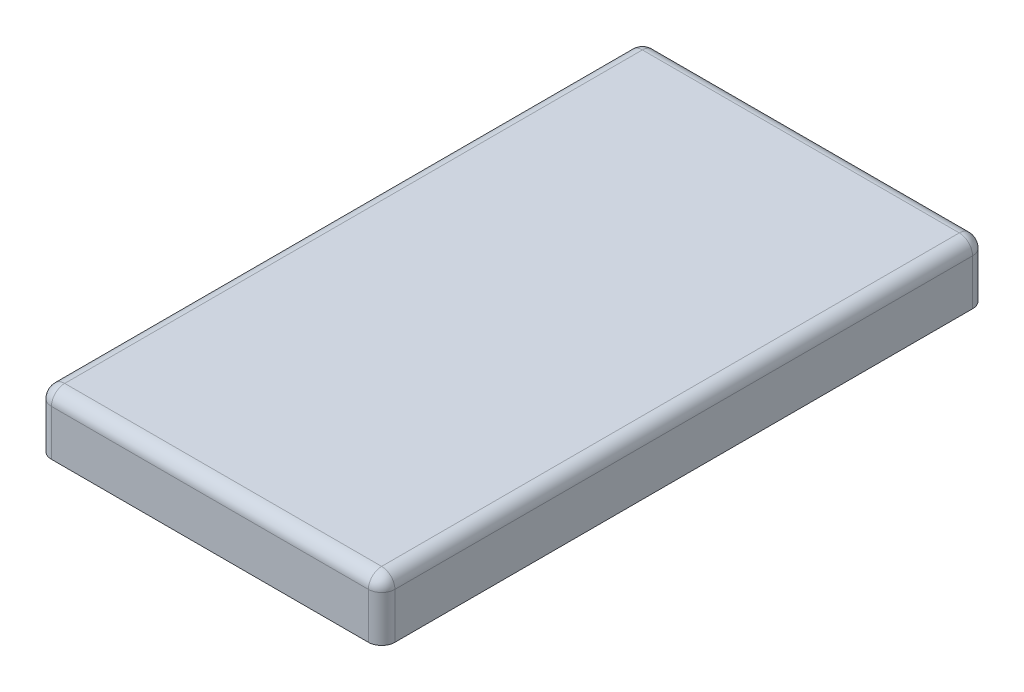
SolidWorks part; units mm, degrees
ref_plane "Face" through (0, 0, 0) normal (0, 0, 1) x (1, 0, 0)
ref_plane "Dessus" through (0, 0, 0) normal (0, 1, 0) x (1, 0, 0)
ref_plane "Droite" through (0, 0, 0) normal (1, 0, 0) x (0, 0, -1)
sketch "Sketch1" plane through (0, 0, 0) normal (0, 1, 0) x (1, 0, 0)
  line L0 (0, -49.53) -> (0, 0) construction
  line L1 (27.94, -49.53) -> (-27.94, -49.53)
  line L2 (27.94, -49.53) -> (27.94, 48.768)
  line L3 (27.94, 48.768) -> (-27.94, 48.768)
  line L4 (-27.94, -49.53) -> (-27.94, 48.768)
  point P0 (0, 0)
  dimension "D1" = 55.88
  dimension "D2" = 49.53
  dimension "D3" = 48.768
extrude "Boss-Extrude1" add sketch "Sketch1" along normal blind 9.62
fillet "Fillet1" radius 2.159 8 edges at (0, 9.62, 49.53) (27.94, 9.62, 0.381) (0, 9.62, -48.768) (-27.94, 9.62, 0.381) (-27.94, 4.81, -48.768) (27.94, 4.81, -48.768) (27.94, 4.81, 49.53) (-27.94, 4.81, 49.53)
sketch "Sketch3" plane through (0, 0, 0) normal (0, -1, 0) x (1, 0, 0)
  line L1 (21.7551, -39.116) -> (-20.5359, -39.116)
  line L2 (21.7551, -39.116) -> (21.7551, 27.0764)
  line L3 (21.7551, 27.0764) -> (-20.5359, 27.0764)
  line L4 (-20.5359, -39.116) -> (-20.5359, 27.0764)
  line L5 (21.7551, -39.116) -> (-20.5359, 27.0764) construction
  line L6 (21.7551, 27.0764) -> (-20.5359, -39.116) construction
  point P0 (0.6096, -6.0198)
  dimension "D1" = 42.291
  dimension "D2" = 27.0764
  dimension "D3" = 39.116
  dimension "D4" = 0.6096
extrude "Cut-Extrude1" cut sketch "Sketch3" against normal blind 7.493
sketch "Sketch4" plane through (0, 0, 0) normal (0, -1, 0) x (1, 0, 0)
  line L0 (21.7551, -39.116) -> (21.7551, 27.0764) construction
  line L1 (-20.5359, -39.116) -> (21.7551, -39.116)
  line L2 (-20.5359, -39.116) -> (-20.5359, -47.268)
  line L3 (-20.5359, -47.268) -> (21.7551, -47.268)
  line L4 (21.7551, -39.116) -> (21.7551, -47.268)
  line L5 (25.781, -48.768) -> (-25.781, -48.768) construction
  dimension "D1" = 1.5
extrude "Cut-Extrude2" cut sketch "Sketch4" against normal blind 5.842
sketch "Sketch6" plane through (0, 0, -48.768) normal (0, 0, -1) x (-1, 0, 0)
  line L0 (18.7579, 0) -> (18.7579, 5.842)
  line L1 (-25.781, 0) -> (25.781, 0) construction
  line L2 (20.5359, 5.842) -> (-21.7551, 5.842) construction
  line L3 (18.7579, 5.842) -> (6.9469, 5.842)
  line L4 (6.9469, 5.842) -> (6.9469, 0)
  line L5 (6.9469, 0) -> (18.7579, 0)
  line L7 (20.5359, 5.842) -> (20.5359, 0) construction
  line L9 (-4.1021, 3.175) -> (4.5339, 3.175)
  line L10 (-4.1021, 3.175) -> (-4.1021, 0)
  line L11 (-4.1021, 0) -> (4.5339, 0)
  line L12 (4.5339, 3.175) -> (4.5339, 0)
  line L13 (-19.8501, 0) -> (-7.9121, 0)
  line L14 (-19.8501, 0) -> (-19.8501, 1.905)
  line L15 (-19.8501, 1.905) -> (-7.9121, 1.905)
  line L16 (-7.9121, 0) -> (-7.9121, 1.905)
  dimension "D1" = 11.811
  dimension "D2" = 1.778
  dimension "D3" = 3.175
  dimension "D4" = 16.002
  dimension "D5" = 8.636
  dimension "D6" = 1.905
  dimension "D7" = 28.448
  dimension "D8" = 11.938
extrude "Cut-Extrude3" cut sketch "Sketch6" against normal blind 4.572
sketch "Sketch7" plane through (0, 0, 0) normal (0, -1, 0) x (1, 0, 0)
  line L6 (-25.781, -47.752) -> (25.781, -47.752)
  line L9 (26.924, 47.371) -> (26.924, -46.609)
  line L10 (-26.924, -46.609) -> (-26.924, 47.371)
  line L11 (-25.781, 48.514) -> (25.781, 48.514)
  line L12 (26.924, 47.371) -> (26.924, -46.609)
  line L13 (-26.924, -46.609) -> (-26.924, 47.371)
  line L14 (-25.781, 48.514) -> (25.781, 48.514)
  arc A9 (25.781, -47.752) -> (26.924, -46.609) centre (25.781, -46.609) ccw
  arc A10 (-26.924, -46.609) -> (-25.781, -47.752) centre (-25.781, -46.609) ccw
  arc A11 (-25.781, 48.514) -> (-26.924, 47.371) centre (-25.781, 47.371) ccw
  arc A12 (26.924, 47.371) -> (25.781, 48.514) centre (25.781, 47.371) ccw
  arc A13 (-26.924, -46.609) -> (-25.781, -47.752) centre (-25.781, -46.609) ccw
  arc A14 (-25.781, 48.514) -> (-26.924, 47.371) centre (-25.781, 47.371) ccw
  arc A15 (26.924, 47.371) -> (25.781, 48.514) centre (25.781, 47.371) ccw
  arc A16 (25.781, -47.752) -> (26.924, -46.609) centre (25.781, -46.609) ccw
  dimension "D1" = 1.016
  dimension "D2" = 1.016
extrude "Cut-Extrude4" cut sketch "Sketch7" against normal blind 3.81
fillet "Fillet2" radius 2.54 1 edges at (0.6096, 3.81, 27.0764)
sketch "Sketch8" plane through (0, 0, 0) normal (0, -1, 0) x (1, 0, 0)
  line L0 (27.94, 47.371) -> (27.94, -46.609) construction
  line L2 (26.924, -46.609) -> (26.924, 47.371) construction
  line L3 (19.8501, -47.752) -> (25.781, -47.752) construction
  line L4 (26.924, -46.609) -> (26.924, -40.386)
  line L5 (21.717, -47.752) -> (25.781, -47.752)
  line L6 (21.717, -47.752) -> (21.717, -40.386)
  line L7 (21.717, -40.386) -> (26.924, -40.386)
  circle A0 centre (23.3172, -43.006) radius 0.508
  arc A1 (25.781, -47.752) -> (26.924, -46.609) centre (25.781, -46.609) ccw construction
  arc A2 (25.781, -47.752) -> (26.924, -46.609) centre (25.781, -46.609) ccw
  dimension "D3" = 1.016
  dimension "D1" = 4.6228
  dimension "D2" = 43.006
  dimension "D4" = 6.223
  dimension "D5" = 40.386
extrude "Boss-Extrude2" add sketch "Sketch8" against normal up to surface (3.81 mm away) up to face at (-3.0607, 3.81, -13.8934)
sketch "Sketch9" plane through (0, 0, 0) normal (0, -1, 0) x (1, 0, 0)
  line L0 (-26.924, 47.371) -> (-26.924, -46.609) construction
  line L1 (-25.781, -47.752) -> (-18.7579, -47.752) construction
  line L2 (-26.924, -40.005) -> (-26.924, -46.609)
  line L3 (-25.781, -47.752) -> (-20.447, -47.752)
  line L4 (-20.447, -47.752) -> (-20.447, -40.005)
  line L5 (-20.447, -40.005) -> (-26.924, -40.005)
  line L6 (-27.94, -46.609) -> (-27.94, 47.371) construction
  arc A0 (-26.924, -46.609) -> (-25.781, -47.752) centre (-25.781, -46.609) ccw construction
  arc A1 (-26.924, -46.609) -> (-25.781, -47.752) centre (-25.781, -46.609) ccw
  circle A2 centre (-23.4188, -43.006) radius 0.508
  circle A3 centre (23.3172, -43.006) radius 0.508 construction
  dimension "D1" = 7.493
  dimension "D2" = 43.006
  dimension "D3" = 3.5052
  dimension "D4" = 40.005
extrude "Boss-Extrude3" add sketch "Sketch9" against normal up to surface (3.81 mm away) up to face at (-4.6996, 3.81, -5.0909)
sketch "Sketch10" plane through (0, 0, 0) normal (0, -1, 0) x (1, 0, 0)
  line L0 (-27.94, -46.609) -> (-27.94, 47.371) construction
  line L1 (-26.924, 47.371) -> (-26.924, -40.005) construction
  line L2 (-26.924, 17.78) -> (-20.447, 17.78)
  line L3 (-26.924, 17.78) -> (-26.924, 26.67)
  line L4 (-26.924, 26.67) -> (-20.447, 26.67)
  line L5 (-20.447, 17.78) -> (-20.447, 26.67)
  circle A0 centre (-23.4188, 23.796) radius 0.508
  circle A1 centre (-23.4188, -43.006) radius 0.508 construction
  dimension "D1" = 4.5212
  dimension "D2" = 23.796
  dimension "D3" = 6.477
  dimension "D4" = 26.67
  dimension "D5" = 17.78
extrude "Boss-Extrude4" add sketch "Sketch10" against normal up to surface (3.81 mm away) up to face at (0.2438, 3.81, 9.0694)
sketch "Sketch11" plane through (0, 0, 0) normal (0, -1, 0) x (1, 0, 0)
  line L0 (26.924, -40.386) -> (26.924, 47.371) construction
  line L1 (26.924, 27.686) -> (21.7502, 27.686)
  line L2 (26.924, 27.686) -> (26.924, 20.32)
  line L3 (26.924, 20.32) -> (21.7502, 20.32)
  line L4 (21.7502, 27.686) -> (21.7502, 20.32)
  circle A0 centre (23.3172, 23.796) radius 0.508
  circle A1 centre (-23.4188, 23.796) radius 0.508 construction
  dimension "D1" = 23.796
  dimension "D2" = 23.3172
  dimension "D3" = 27.686
  dimension "D4" = 20.32
  dimension "D5" = 21.7502
extrude "Boss-Extrude5" add sketch "Sketch11" against normal up to surface (3.81 mm away) up to face at (0.2438, 3.81, 22.4044)
fillet "Fillet3" radius 1.27 6 edges at (21.717, 1.905, -40.386) (-20.447, 1.905, -40.005) (21.7502, 1.905, 20.32) (21.7502, 1.905, 27.686) (-20.447, 1.905, 17.78) (-20.447, 1.905, 26.67)
hole_wizard "#0-80 Tapped Hole1" positions "Sketch12" profile "Sketch14" tap size "#0-80" standard "ANSI Inch"
sketch "Sketch12" plane through (0, 0, 0) normal (0, -1, 0) x (-1, 0, 0)
  point P0 (-23.3172, 43.006)
  point P4 (23.4188, 43.006)
  point P7 (23.4188, -23.796)
  point P10 (-23.3172, -23.796)
sketch "Sketch14" plane through (23.3172, 0, -43.006) normal (1, 0, 0) x (0, 0, -1)
  line L0 (0, 0) -> (0, 6.9111)
  line L1 (0, 6.9111) -> (0.5956, 6.5532)
  line L2 (0.5956, 6.5532) -> (0.5956, 0)
  line L5 (0.5956, 0) -> (0, 0)
  line L10 (0, 6.9111) -> (-0.5956, 6.5532) construction
  line L11 (0, -6.35) -> (0, 107.95) construction
  dimension "Tap Drill Dia." = 1.1913
  dimension "Tap Drill Depth" = 6.5532
  dimension "Drill Angle" = 118
cosmetic thread "Hole Thread1" parameters "D1"=3.048, "D2"=1.524
cosmetic thread "Hole Thread2" parameters "D1"=3.048, "D2"=1.524
cosmetic thread "Hole Thread3" parameters "D1"=3.048, "D2"=1.524
cosmetic thread "Hole Thread4" parameters "D1"=3.048, "D2"=1.524
